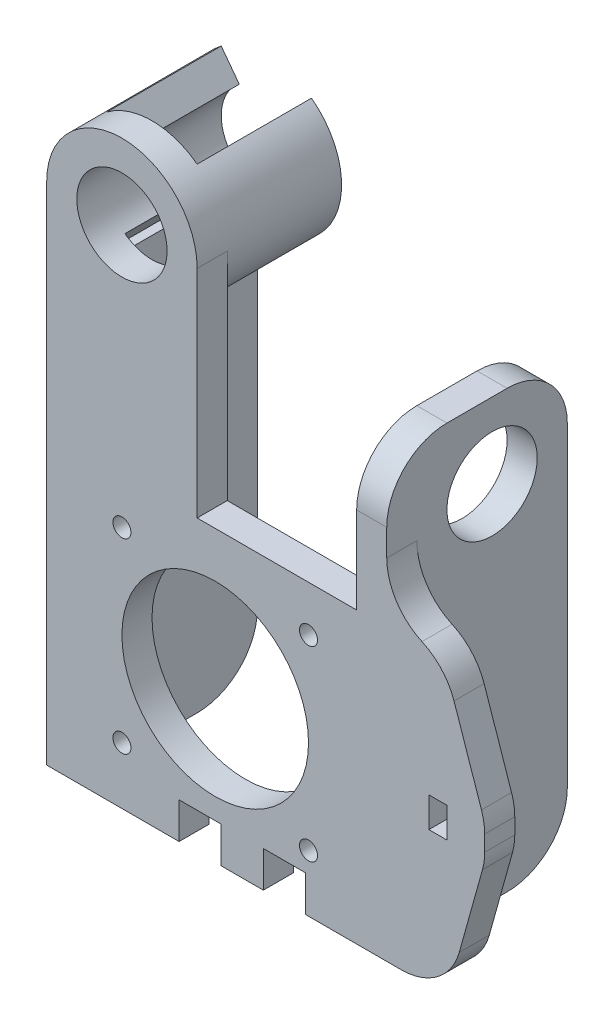
SolidWorks part; units mm, degrees
material "ABS"
ref_plane "Front Plane" through (0, 0, 0) normal (0, 0, 1) x (1, 0, 0)
ref_plane "Top Plane" through (0, 0, 0) normal (0, 1, 0) x (1, 0, 0)
ref_plane "Right Plane" through (0, 0, 0) normal (1, 0, 0) x (0, 0, -1)
sketch "Sketch1" plane through (0, 0, 0) normal (0, 0, 1) x (1, 0, 0)
  line L0 (-15.5, 59) -> (-15.5, 15.5) construction
  line L1 (15.5, -15.5) -> (-15.5, -15.5) construction
  line L2 (15.5, -15.5) -> (15.5, 15.5) construction
  line L3 (15.5, 15.5) -> (-15.5, 15.5) construction
  line L4 (-15.5, -15.5) -> (-15.5, 15.5) construction
  line L5 (15.5, -15.5) -> (-15.5, 15.5) construction
  line L6 (15.5, 15.5) -> (-15.5, -15.5) construction
  line L7 (-21, -21) -> (21, -21) construction
  line L8 (-21, -21) -> (-21, 21) construction
  line L9 (-21, 21) -> (21, 21) construction
  line L10 (21, -21) -> (21, 21) construction
  line L11 (-21, -21) -> (21, 21) construction
  line L12 (-21, 21) -> (21, -21) construction
  line L13 (35.5, -2.5) -> (38.5, -2.5)
  line L14 (35.5, -2.5) -> (35.5, 2.5)
  line L15 (35.5, 2.5) -> (38.5, 2.5)
  line L16 (38.5, -2.5) -> (38.5, 2.5)
  line L17 (35.5, -2.5) -> (38.5, 2.5) construction
  line L18 (35.5, 2.5) -> (38.5, -2.5) construction
  line L19 (-28, 59) -> (-28, -24.9678)
  line L20 (-28, -24.9678) -> (38.5, -24.9678)
  line L21 (38.5, -24.9678) -> (44.7697, -2.5)
  line L22 (44.7697, -2.5) -> (44.7697, 3.1424)
  line L23 (44.7697, 3.1424) -> (37.9804, 23.0908)
  line L24 (37.9804, 23.0908) -> (-3, 23.0908)
  line L25 (-3, 23.0908) -> (-3, 59)
  circle A0 centre (0, 0) radius 15.5
  circle A1 centre (-15.5, 15.5) radius 1.5
  circle A2 centre (-15.5, -15.5) radius 1.5
  circle A3 centre (15.5, -15.5) radius 1.5
  circle A4 centre (15.5, 15.5) radius 1.5
  circle A5 centre (-15.5, 59) radius 7.5
  arc A6 (-28, 59) -> (-3, 59) centre (-15.5, 59) cw
  point P0 (0, 0)
  point P18 (37, 0)
  point P23 (-15.5, 37.25)
  dimension "D2" = 3
  dimension "D3" = 15
  dimension "D8" = 38
  dimension "D9" = 5
  dimension "D1" = 31
  dimension "D4" = 42
  dimension "D5" = 37
  dimension "D6" = 3
  dimension "D7" = 5
extrude "Boss-Extrude1" add sketch "Sketch1" along normal blind 5
sketch "Sketch3" plane through (0, 0, 5) normal (0, 0, 1) x (1, 0, 0)
  line L0 (-28, -24.9678) -> (38.5, -24.9678) construction
  line L1 (23.5, -24.9678) -> (28.5, -24.9678)
  line L2 (23.5, -24.9678) -> (23.5, 47.5)
  line L3 (23.5, 47.5) -> (28.5, 47.5)
  line L4 (28.5, -24.9678) -> (28.5, 47.5)
  line L5 (23.5, 35) -> (28.5, 35) construction
  line L7 (-28, -24.9678) -> (-23, -24.9678)
  line L8 (-28, -24.9678) -> (-28, 47.5)
  line L9 (-28, 47.5) -> (-23, 47.5)
  line L10 (-23, -24.9678) -> (-23, 47.5)
  circle A0 centre (-15.5, 59) radius 7.5 construction
  circle A2 centre (15.5, 15.5) radius 1.5 construction
  dimension "D1" = 5
  dimension "D2" = 24
  dimension "D3" = 12.5
  dimension "D4" = 8
extrude "Boss-Extrude3" add sketch "Sketch3" against normal blind 30
sketch "Sketch4" plane through (28.5, 0, 0) normal (1, 0, 0) x (0, 0, -1)
  line L1 (12.5, 35) -> (25, 35) construction
  line L2 (12.5, 35) -> (12.5, 47.5) construction
  line L3 (12.5, 47.5) -> (25, 47.5) construction
  line L4 (25, 35) -> (25, 47.5) construction
  circle A0 centre (12.5, 35) radius 7.5
  dimension "D1" = 15
  dimension "D2" = 12.5
extrude "Cut-Extrude1" cut sketch "Sketch4" against normal through all
sketch "Sketch5" plane through (0, 0, 0) normal (0, 0, -1) x (-1, 0, 0)
  circle A0 centre (15.5, 59) radius 7.5
  circle A1 centre (15.5, 59) radius 12.5
extrude "Boss-Extrude4" add sketch "Sketch5" along normal blind 19
sketch "Sketch7" plane through (0, 0, -19) normal (0, 0, -1) x (-1, 0, 0)
  line L0 (11, 65) -> (8, 69)
  line L1 (20, 65) -> (23, 69)
  line L2 (11, 53) -> (8, 49)
  line L3 (20, 53) -> (23, 49)
  arc A0 (8, 49) -> (23, 49) centre (15.5, 59) ccw
  arc A1 (11, 53) -> (20, 53) centre (15.5, 59) ccw
  arc A2 (20, 65) -> (11, 65) centre (15.5, 59) ccw
  arc A3 (23, 69) -> (8, 69) centre (15.5, 59) ccw
extrude "Cut-Extrude2" cut sketch "Sketch7" against normal up to surface (19 mm away) up to face at (17, 15.5, 0)
fillet "Fillet4" radius 10 6 edges at (-25.5, -24.9678, -25) (26, -24.9678, -25) (28.5, 23.0908, 2.5) (26, 47.5, 5) (26, 47.5, -25) (-25.5, 47.5, -25)
fillet "Fillet5" radius 10 4 edges at (38.5, -24.9678, 2.5) (44.7697, -2.5, 2.5) (44.7697, 3.1424, 2.5) (37.9804, 23.0908, 2.5)
sketch "Sketch9" plane through (0, 0, 5) normal (0, 0, 1) x (1, 0, 0)
  line L0 (-28, -24.9678) -> (30.9085, -24.9678) construction
  line L1 (-6, -24.9678) -> (1, -24.9678)
  line L2 (-6, -24.9678) -> (-6, -18.9678)
  line L3 (-6, -18.9678) -> (1, -18.9678)
  line L4 (1, -24.9678) -> (1, -18.9678)
  line L5 (1, -24.9678) -> (8, -24.9678) construction
  line L6 (8, -24.9678) -> (15, -24.9678)
  line L7 (8, -24.9678) -> (8, -18.9678)
  line L8 (8, -18.9678) -> (15, -18.9678)
  line L9 (15, -24.9678) -> (15, -18.9678)
  point P10 (4.5, -24.9678)
  dimension "D1" = 6
  dimension "D2" = 7
  dimension "D3" = 7
  dimension "D4" = 4.5
extrude "Cut-Extrude3" cut sketch "Sketch9" against normal through all
equation "\"pulley_pitch_diam\"= 12.73mm"
equation "\"pulley_total_width\"= 16mm"
equation "\"pulley_total_diam\"= 16mm"
equation "\"belt_width\"= 6mm"
equation "\"material_thickness\"= 3mm"
equation "\"shaft_diam\"= 8mm"
equation "\"bearing_od\"= 22mm"
equation "\"bearing_thickness\"= 7mm"
